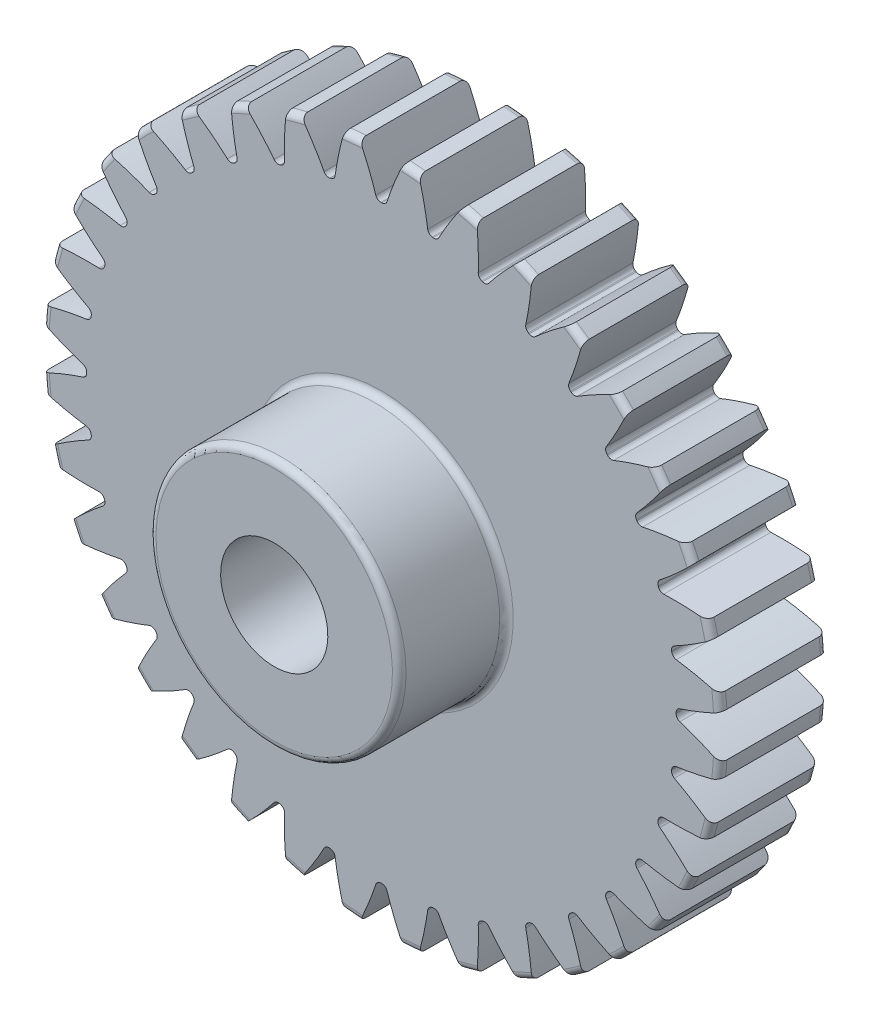
SolidWorks part; units mm, degrees
material "Delrin 2700 NC010, Low Viscosity Acetal Copolymer (SS)"
ref_plane "Front Plane" through (0, 0, 0) normal (0, 0, 1) x (1, 0, 0)
ref_plane "Top Plane" through (0, 0, 0) normal (0, 1, 0) x (1, 0, 0)
ref_plane "Right Plane" through (0, 0, 0) normal (1, 0, 0) x (0, 0, -1)
sketch "Sketch1" plane through (0, 0, 0) normal (0, 0, 1) x (1, 0, 0)
  line L0 (-457.2, 0) -> (457.2, 0) construction
  circle A0 centre (0, 0) radius 19 construction
  circle A1 centre (0, 0) radius 18 construction
  circle A2 centre (0, 0) radius 16.5 construction
  circle A3 centre (0, 0) radius 7 construction
  circle A4 centre (0, 0) radius 3 construction
  dimension "D2" = 1
  dimension "D3" = 2.5
  dimension "D1" = 2.5
sketch "Sketch2" plane through (0, 0, 0) normal (1, 0, 0) x (0, 0, -1)
  line L0 (0, 0) -> (-6, 0) construction
  line L1 (-6, 0) -> (-12, 0) construction
  dimension "Overall Width" = 12
  dimension "Face Width" = 6
sketch "Sketch4" plane through (0, 0, 0) normal (1, 0, 0) x (0, 0, -1)
  line L0 (-12, 3) -> (-12, 7)
  line L1 (-12, 7) -> (-6, 7)
  line L2 (-6, 7) -> (-6, 19)
  line L3 (-6, 19) -> (0, 19)
  line L4 (0, 19) -> (0, 3)
  line L5 (-6, 7) -> (-6, 0) construction
  line L6 (0, 19) -> (0, -19) construction
  line L7 (-6, 7) -> (0, 7) construction
  line L12 (-12, 3) -> (0, 3)
revolve "Revolve1" add sketch "Sketch4" angle 360 about L1
fillet "Fillet2" radius 0.38 4 edges at (0, 7, 12) (0, 7, 6) (0, 19, 6) (0, 19, 0)
sketch "Sketch7" plane through (0, 0, 6) normal (0, 0, 1) x (1, 0, 0)
  line L0 (0, 0) -> (0, 19) construction
  line L1 (0.7851, 17.9829) -> (1.191, 18.9626) construction
  line L3 (1.656, 18.9277) -> (1.5688, 17.9315) construction
  line L4 (1.5688, 17.9315) -> (1.4381, 16.4372) construction
  line L5 (0, 0) -> (1.4381, 16.4372) construction
  line L6 (0.7851, 17.9829) -> (0, 0) construction
  line L7 (0.7851, 17.9829) -> (0.8288, 18.9819) construction
  line L8 (0.7851, 17.9829) -> (0, 0) construction
  circle A0 centre (0, 0) radius 19 construction
  arc A1 (-0.0266, 16.5) -> (0.0266, 16.5) centre (0, 0) cw
  circle A2 centre (0, 0) radius 16.5 construction
  arc A3 (-0.7851, 17.9829) -> (0.7851, 17.9829) centre (0, 0) cw construction
  circle A4 centre (0, 0) radius 18 construction
  arc A5 (2.0864, 18.8851) -> (1.2246, 18.9605) centre (0, 0) ccw construction
  arc A6 (0.7851, 17.9829) -> (2.3495, 17.846) centre (0, 0) cw construction
  arc A7 (-1.2246, 18.9605) -> (1.2246, 18.9605) centre (0, 0) cw
  arc A8 (0.3122, 16.7065) -> (1.2246, 18.9605) centre (17.415, 11.0946) cw
  arc A9 (-0.3122, 16.7065) -> (-1.2246, 18.9605) centre (-17.415, 11.0946) ccw
  arc A10 (-0.0266, 16.5) -> (-0.3122, 16.7065) centre (-0.0271, 16.8) cw
  arc A11 (0.0266, 16.5) -> (0.3122, 16.7065) centre (0.0271, 16.8) ccw
  point P26 (-0.2452, 16.4982)
  point P29 (0.2452, 16.4982)
  dimension "D4" = 0.3
  dimension "D5" = 18
  dimension "D3" = 20
  dimension "D1" = 3.1416
  dimension "D2" = 1.5708
extrude "Cut-Extrude2" cut sketch "Sketch7" against normal through all
pattern_circular "CirPattern1" count 36 over 360 about axis through (0, 0, 12) along (0, 0, -1) of "Cut-Extrude2"
ref_axis "Axis1" through (0, 0, 12) along (0, 0, -1)
equation "\"D1@Sketch1\"=2.5*(\"Pitch Dia.@Sketch1\"/\"Number of Teeth@Sketch1\")"
equation "\"D1@CirPattern1\"=\"Number of Teeth@Sketch1\""
equation "\"D1@Fillet2\"=\"OD@Sketch1\"*.01"
equation "\"D1@Sketch7\"=3.14159*(\"Pitch Dia.@Sketch1\"/\"Number of Teeth@Sketch1\")"
equation "\"D2@Sketch7\"=\"D1@Sketch7\"/2"
equation "\"D4@Sketch7\"=\"D1@Sketch7\"*.0955"
equation "\"D5@Sketch7\"=\"Pitch Dia.@Sketch1\"/2"
